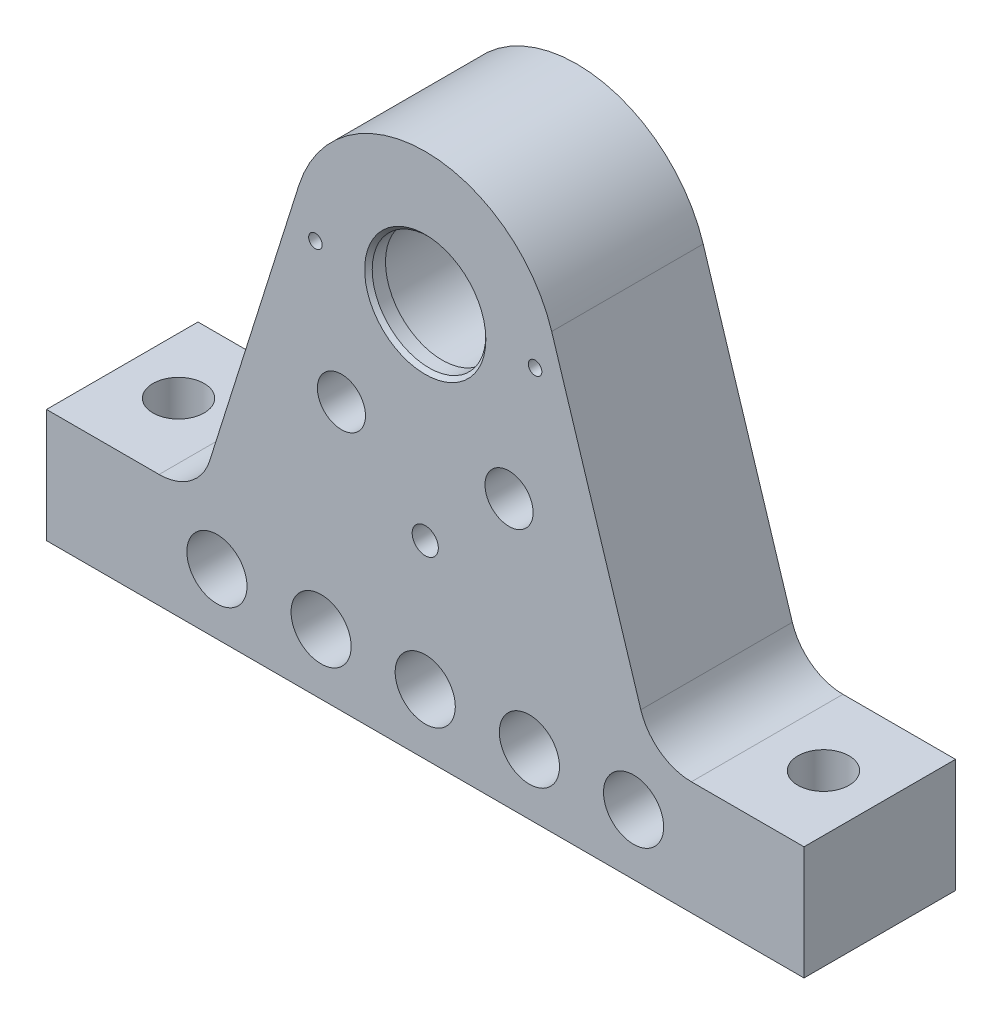
SolidWorks part; units mm, degrees
material "AISI 316 Annealed Stainless Steel Bar (SS)"
ref_plane "Front" through (0, 0, 0) normal (0, 0, 1) x (1, 0, 0)
ref_plane "Top" through (0, 0, 0) normal (0, 1, 0) x (1, 0, 0)
ref_plane "Right" through (0, 0, 0) normal (1, 0, 0) x (0, 0, -1)
sketch "Sketch1" plane through (0, 0, 0) normal (0, 0, 1) x (1, 0, 0)
  line L0 (-50, 0) -> (50, 0)
  line L1 (50, 0) -> (50, 15)
  line L3 (-50, 15) -> (-50, 0)
  line L4 (0, 0) -> (0, 52) construction
  line L5 (0, 52) -> (16.6918, 57.2568) construction
  line L6 (0, 52) -> (-16.6918, 57.2568) construction
  line L7 (50, 15) -> (30, 15)
  line L8 (-50, 15) -> (-30, 15)
  line L11 (-16.6918, 57.2568) -> (-30, 15)
  line L12 (16.6918, 57.2568) -> (30, 15)
  arc A0 (16.6918, 57.2568) -> (-16.6918, 57.2568) centre (0, 52) ccw
  circle A3 centre (0, 52) radius 4.7625 construction
  dimension "D3" = 17.5
  dimension "D6" = 9.525
  dimension "D1" = 100
  dimension "D2" = 52
  dimension "D4" = 15
  dimension "D5" = 20
extrude "Boss-Extrude1" add sketch "Sketch1" along normal blind 20
fillet "Fillet1" radius 7 2 edges at (30, 15, 10) (-30, 15, 10)
hole_wizard "CBORE for #8 Socket Head Cap Screw1" positions "Sketch2" profile "Sketch3" counterbore size "#8" standard "ANSI Inch" end condition through all
sketch "Sketch2" plane through (0, 0, 20) normal (0, 0, 1) x (1, 0, 0)
  line L0 (0, 0) -> (0, 8)
  line L1 (-50, 0) -> (50, 0) construction
  line L3 (-27.5, 8) -> (0, 8)
  line L5 (0, 8) -> (27.5, 8)
  point P0 (0, 8)
  point P21 (-27.5, 8)
  point P22 (-13.75, 8)
  point P24 (13.75, 8)
  point P28 (27.5, 8)
  dimension "D1" = 8
  dimension "D2" = 27.5
sketch "Sketch3" plane through (0, 8, 20) normal (1, 0, 0) x (0, -1, 0)
  line L0 (0, 0) -> (0, 20)
  line L1 (0, 20) -> (2.2479, 20)
  line L3 (2.2479, 20) -> (2.2479, 10)
  line L4 (2.2479, 10) -> (3.9687, 10)
  line L5 (3.9687, 10) -> (3.9687, 0)
  line L7 (3.9687, 0) -> (0, 0)
  line L11 (0, -6.35) -> (0, 107.95) construction
  dimension "Thru Hole Dia." = 4.4958
  dimension "Thru Hole Depth" = 20
  dimension "C'Bore Dia." = 7.9375
  dimension "C'Bore Depth" = 10
sketch "Sketch4" plane through (0, 0, 0) normal (1, 0, 0) x (0, 0, -1)
  line L0 (0, 52) -> (-20, 52)
  line L1 (-20, 52) -> (-20, 44.5)
  line L2 (-20, 44.5) -> (-17.75, 44.5)
  line L3 (-17.75, 44.5) -> (-17.75, 44)
  line L4 (-17.75, 44) -> (-7, 44)
  line L5 (-7, 44) -> (-7, 41)
  line L6 (-7, 41) -> (0, 41)
  line L7 (0, 0) -> (0, 52) construction
  line L8 (0, 41) -> (0, 52)
  point P3 (-10, 52)
  dimension "D1" = 11
  dimension "D2" = 8
  dimension "D3" = 7.5
  dimension "D4" = 2.25
  dimension "D5" = 7
revolve "Cut-Revolve1" cut sketch "Sketch4" angle 360 about L0
hole_wizard "#2-56 Tapped Hole1" positions "Sketch5" profile "Sketch6" tap size "#2-56" standard "ANSI Inch"
sketch "Sketch5" plane through (0, 0, 20) normal (0, 0, 1) x (1, 0, 0)
  line L0 (14.5, 52) -> (-14.5, 52) construction
  line L3 (0, 0) -> (0, 52) construction
  line L4 (-50, 0) -> (50, 0) construction
  circle A1 centre (0, 52) radius 7.5 construction
  point P0 (14.5, 52)
  point P2 (-14.5, 52)
  dimension "D1" = 29
sketch "Sketch6" plane through (14.5, 52, 20) normal (1, 0, 0) x (0, -1, 0)
  line L0 (0, 0) -> (0, 6.2642)
  line L1 (0, 6.2642) -> (0.889, 5.73)
  line L2 (0.889, 5.73) -> (0.889, 0)
  line L5 (0.889, 0) -> (0, 0)
  line L10 (0, 6.2642) -> (-0.889, 5.73) construction
  line L11 (0, -6.35) -> (0, 107.95) construction
  dimension "Tap Drill Dia." = 1.778
  dimension "Tap Drill Depth" = 5.73
  dimension "Drill Angle" = 118
cosmetic thread "Hole Thread1" parameters "D1"=4.37, "D2"=2.1844
cosmetic thread "Hole Thread2" parameters "D1"=4.37, "D2"=2.1844
chamfer "Chamfer1" distance 0.5 angle 45 2 edges at (-7.5, 52, 20) (-11, 52, 0)
hole_wizard "1/8 (0.1250) Dowel Hole1" positions "Sketch9" profile "Sketch10" hole size "1/8" standard "ANSI Inch"
sketch "Sketch9" plane through (0, 0, 0) normal (0, 0, -1) x (-1, 0, 0)
  line L0 (27.5, 8) -> (13.75, 8) construction
  point P0 (20.625, 8)
sketch "Sketch10" plane through (-20.625, 8, 0) normal (1, 0, 0) x (0, 1, 0)
  line L0 (0, 0) -> (0, 6.9539)
  line L1 (0, 6.9539) -> (1.5875, 6)
  line L2 (1.5875, 6) -> (1.5875, 0)
  line L5 (1.5875, 0) -> (0, 0)
  line L10 (0, 6.9539) -> (-1.5875, 6) construction
  line L11 (0, -6.35) -> (0, 107.95) construction
  dimension "Hole Dia." = 3.175
  dimension "Hole Depth" = 6
  dimension "Drill Angle" = 118
hole_wizard "1/8 (0.1250) Dowel Slot1" positions "Sketch11" profile "Sketch12" size "1/8" standard "ANSI Inch" slot yes
sketch "Sketch11" plane through (0, 0, 0) normal (0, 0, -1) x (-1, 0, 0)
  line L0 (-18.625, 8) -> (-22.625, 8) construction
  line L1 (-13.75, 8) -> (-27.5, 8) construction
  point P0 (-20.625, 8)
  dimension "D1" = 4
sketch "Sketch12" plane through (20.625, 8, 0) normal (1, 0, 0) x (0, 1, 0)
  line L0 (0, 0) -> (0, 6.9539)
  line L1 (0, 6.9539) -> (1.5875, 6)
  line L2 (1.5875, 6) -> (1.5875, 0)
  line L5 (1.5875, 0) -> (0, 0)
  line L10 (0, 6.9539) -> (-1.5875, 6) construction
  line L11 (0, -6.35) -> (0, 107.95) construction
  dimension "Hole Dia." = 3.175
  dimension "Hole Depth" = 6
  dimension "Drill Angle" = 118
sketch "Sketch13" plane through (0, 0, 0) normal (0, 0, -1) x (-1, 0, 0)
  circle A0 centre (0, 52) radius 10
  dimension "D1" = 20
extrude "Cut-Extrude1" [suppressed] cut sketch "Sketch13" along normal blind 1.1 from offset 2 offset against normal yes
hole_wizard "1/4 Clearance Hole1" positions "Sketch16" profile "Sketch17" hole size "1/4" standard "ANSI Inch" end condition through all
sketch "Sketch16" plane through (0, 15, 0) normal (0, 1, 0) x (1, 0, 0)
  line L0 (50, -10) -> (35.1344, -10) construction
  line L1 (50, -20) -> (50, 0) construction
  line L4 (-35.1344, -10) -> (-50, -10) construction
  line L6 (-50, -20) -> (-50, 0) construction
  line L7 (-35.1344, -20) -> (-35.1344, 0) construction
  line L8 (35.1344, 0) -> (35.1344, -20) construction
  point P0 (42.5672, -10)
  point P2 (-42.5672, -10)
sketch "Sketch17" plane through (42.5672, 15, 10) normal (1, 0, 0) x (0, 0, 1)
  line L0 (0, 0) -> (0, 15)
  line L1 (0, 15) -> (3.3782, 15)
  line L2 (3.3782, 15) -> (3.3782, 0)
  line L5 (3.3782, 0) -> (0, 0)
  line L11 (0, -6.35) -> (0, 107.95) construction
  dimension "Thru Hole Dia." = 6.7564
  dimension "Thru Hole Depth" = 15
hole_wizard "#8-32 Tapped Hole1" positions "Sketch18" profile "Sketch19" tap size "#8-32" standard "ANSI Inch"
sketch "Sketch18" plane through (0, 0, 20) normal (0, 0, 1) x (1, 0, 0)
  line L0 (0, 0) -> (0, 25) construction
  line L1 (-50, 0) -> (50, 0) construction
  point P0 (0, 25)
  dimension "D1" = 25
sketch "Sketch19" plane through (0, 25, 20) normal (1, 0, 0) x (0, -1, 0)
  line L0 (0, 0) -> (0, 11.7478)
  line L1 (0, 11.7478) -> (1.7272, 10.71)
  line L2 (1.7272, 10.71) -> (1.7272, 0)
  line L5 (1.7272, 0) -> (0, 0)
  line L10 (0, 11.7478) -> (-1.7272, 10.71) construction
  line L11 (0, -6.35) -> (0, 107.95) construction
  dimension "Tap Drill Dia." = 3.4544
  dimension "Tap Drill Depth" = 10.71
  dimension "Drill Angle" = 118
cosmetic thread "Hole Thread3" parameters "D1"=8.33, "D2"=4.1656
hole_wizard "1/4 (0.2500) Dowel Hole1" positions "Sketch20" profile "Sketch21" hole size "1/4" standard "ANSI Inch" end condition through all
sketch "Sketch20" plane through (0, 0, 20) normal (0, 0, 1) x (1, 0, 0)
  line L0 (50, 0) -> (11.0618, 35.3314) construction
  line L1 (11.0618, 35.3314) -> (-11.0618, 35.3314) construction
  line L4 (0, 0) -> (0, 35.3314) construction
  line L5 (-50, 0) -> (50, 0) construction
  point P0 (-11.0618, 35.3314)
  point P2 (11.0618, 35.3314)
  dimension "D1" = 38.9382
  dimension "D2" = 35.3314
sketch "Sketch21" plane through (-11.0618, 35.3314, 20) normal (1, 0, 0) x (0, -1, 0)
  line L0 (0, 0) -> (0, 20)
  line L1 (0, 20) -> (3.175, 20)
  line L2 (3.175, 20) -> (3.175, 0)
  line L5 (3.175, 0) -> (0, 0)
  line L11 (0, -6.35) -> (0, 107.95) construction
  dimension "Thru Hole Dia." = 6.35
  dimension "Thru Hole Depth" = 20
